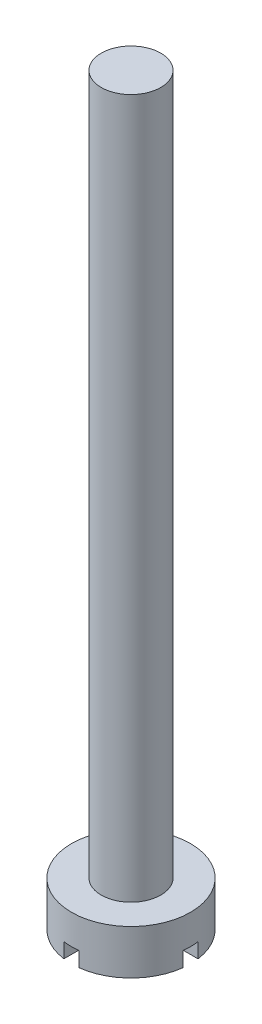
SolidWorks part; units mm, degrees
ref_plane "Front Plane" through (0, 0, 0) normal (0, 0, 1) x (1, 0, 0)
ref_plane "Top Plane" through (0, 0, 0) normal (0, 1, 0) x (1, 0, 0)
ref_plane "Right Plane" through (0, 0, 0) normal (1, 0, 0) x (0, 0, -1)
sketch "Sketch1" plane through (0, 0, 0) normal (0, 1, 0) x (1, 0, 0)
  circle A0 centre (0, 0) radius 4
  circle A1 centre (0, 0) radius 2
  dimension "D1" = 4
  dimension "D2" = 8
extrude "Boss-Extrude1" add sketch "Sketch1" along normal blind 3
extrude "Boss-Extrude2" add sketch "Sketch1<3>" along normal blind 50 contours A1 region at (0, 0, 0)
sketch "Sketch1<3>" plane through (0, 0, 0) normal (0, 1, 0) x (1, 0, 0) same geometry as "Sketch1"
sketch "Sketch2" plane through (0, 0, 0) normal (0, -1, 0) x (-1, 0, 0)
  line L1 (-0.4638, 4.19) -> (0.5481, 4.19)
  line L2 (-0.4638, 4.19) -> (-0.4638, -4.3376)
  line L3 (-0.4638, -4.3376) -> (0.5481, -4.3376)
  line L4 (0.5481, 4.19) -> (0.5481, -4.3376)
  line L5 (-4.385, 0.5429) -> (4.3323, 0.5429)
  line L6 (-4.385, 0.5429) -> (-4.385, -0.4691)
  line L7 (-4.385, -0.4691) -> (4.3323, -0.4691)
  line L8 (4.3323, 0.5429) -> (4.3323, -0.4691)
  circle M1 centre (0, 0) radius 4
extrude "Cut-Extrude1" cut sketch "Sketch2" against normal blind 1 contours L2 L5 L4 M1 | L2 L7 L4 L5 | L4 L7 L5 M1 | L7 L2 L5 M1 | L2 L3 L4 L1 region at (-0.0419, 0, -2.266) region at (-0.0422, 0, -0.0369) region at (2.2265, 0, -0.0367) region at (-2.2686, 0, -0.0367)
